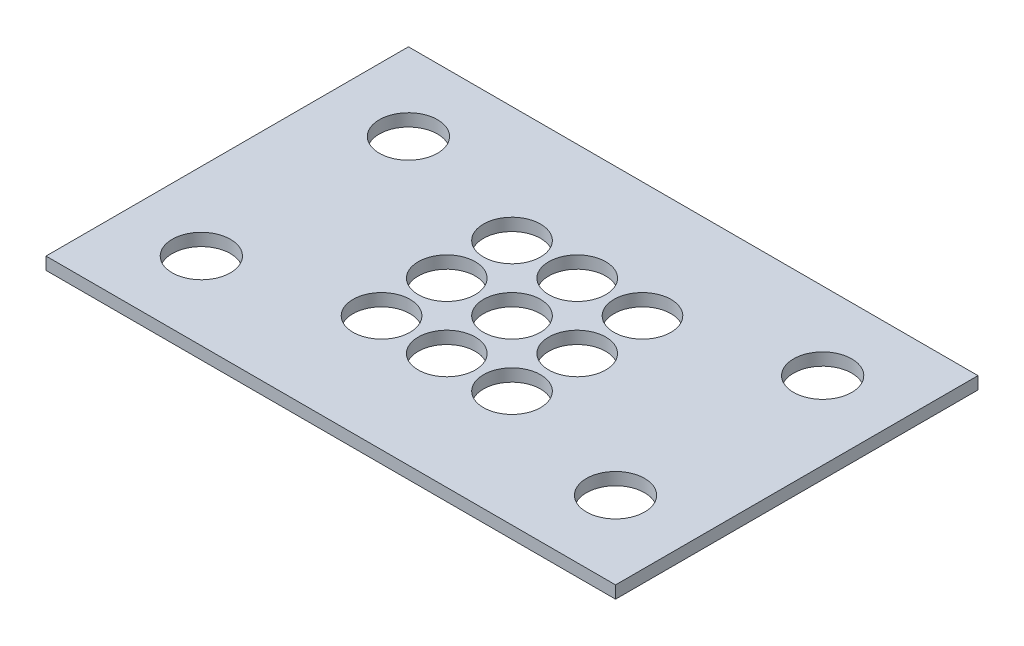
SolidWorks part; units mm, degrees
ref_plane "Front Plane" through (0, 0, 0) normal (0, 0, 1) x (1, 0, 0)
ref_plane "Top Plane" through (0, 0, 0) normal (0, 1, 0) x (1, 0, 0)
ref_plane "Right Plane" through (0, 0, 0) normal (1, 0, 0) x (0, 0, -1)
sketch "Sketch1" plane through (0, 0, 0) normal (0, 1, 0) x (1, 0, 0)
  line L0 (9.525, 34.925) -> (0, 34.925) construction
  line L1 (0, 0) -> (69.85, 0)
  line L2 (0, 0) -> (0, 44.45)
  line L3 (0, 44.45) -> (69.85, 44.45)
  line L4 (69.85, 0) -> (69.85, 44.45)
  line L5 (9.525, 34.925) -> (60.325, 34.925) construction
  line L6 (9.525, 34.925) -> (9.525, 9.525) construction
  line L7 (9.525, 9.525) -> (60.325, 9.525) construction
  line L8 (60.325, 34.925) -> (60.325, 9.525) construction
  line L9 (9.525, 34.925) -> (9.525, 44.45) construction
  circle A0 centre (9.525, 34.925) radius 3.5687
  circle A1 centre (60.325, 34.925) radius 3.5687
  circle A2 centre (9.525, 9.525) radius 3.5687
  circle A3 centre (60.325, 9.525) radius 3.5687
  circle A4 centre (34.925, 22.225) radius 3.5
  circle A5 centre (42.925, 22.225) radius 3.5
  circle A6 centre (42.925, 30.225) radius 3.5
  circle A7 centre (34.925, 30.225) radius 3.5
  circle A8 centre (42.925, 22.225) radius 3.5
  circle A9 centre (42.925, 14.225) radius 3.5
  circle A10 centre (34.925, 14.225) radius 3.5
  circle A11 centre (26.925, 22.225) radius 3.5
  circle A12 centre (26.925, 30.225) radius 3.5
  circle A13 centre (34.925, 30.225) radius 3.5
  circle A14 centre (26.925, 22.225) radius 3.5
  circle A15 centre (26.925, 14.225) radius 3.5
  circle A16 centre (34.925, 14.225) radius 3.5
  point P13 (34.925, 34.925)
  point P14 (34.925, 44.45)
  point P20 (69.85, 22.225)
  dimension "D5" = 7.1374
  dimension "D6" = 7
  dimension "D1" = 69.85
  dimension "D2" = 44.45
  dimension "D3" = 50.8
  dimension "D4" = 25.4
  dimension "D15" = 8
  dimension "D16" = 8
  dimension "D7" = 2
  dimension "D8" = 2
  dimension "D9" = 2
  dimension "D10" = 2
  dimension "D11" = 2
  dimension "D12" = 2
  dimension "D13" = 2
  dimension "D14" = 2
extrude "Boss-Extrude1" add sketch "Sketch1" along normal blind 1.524 contours L1 L4 L3 L2 A15 A12 A11 A10 A9 A7 A6 A5 A4 A3 A2 A1 A0 region at (0.8279, 0, -22.225)
